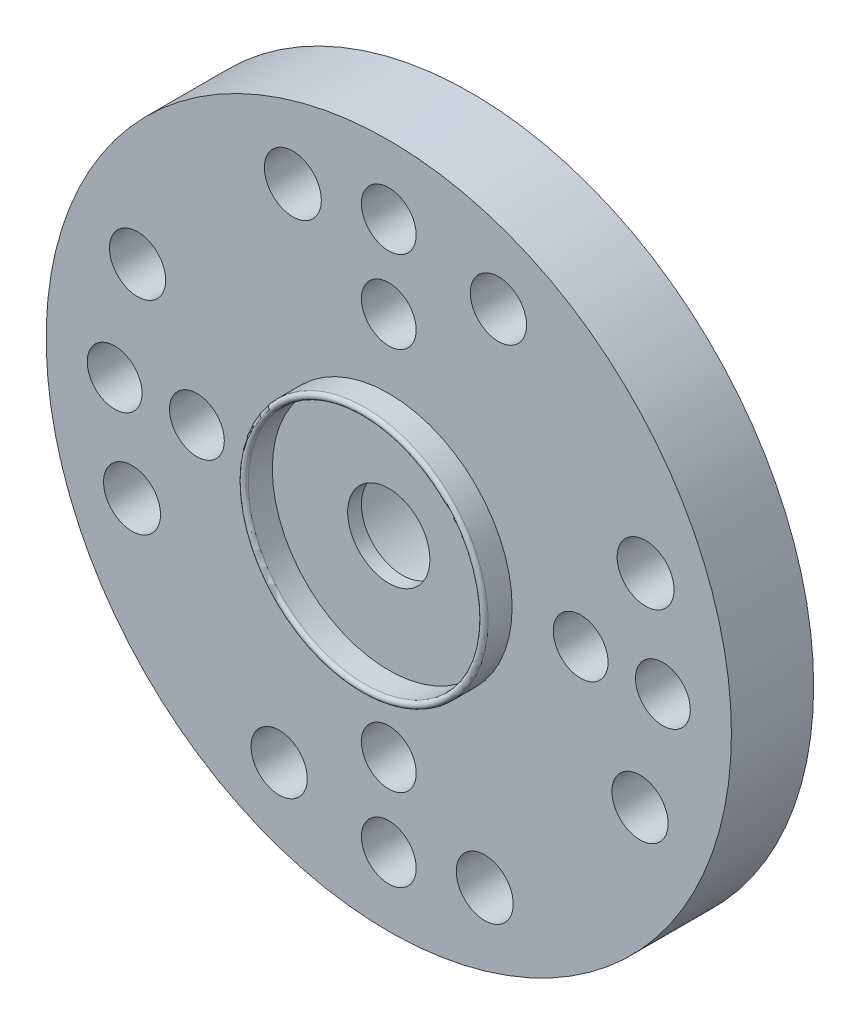
SolidWorks part; units mm, degrees
ref_plane "Plan de face" through (0, 0, 0) normal (0, 0, 1) x (1, 0, 0)
ref_plane "Plan de dessus" through (0, 0, 0) normal (0, 1, 0) x (1, 0, 0)
ref_plane "Plan de droite" through (0, 0, 0) normal (1, 0, 0) x (0, 0, -1)
sketch "Esquisse1" plane through (0, 0, 0) normal (0, 0, 1) x (1, 0, 0)
  circle A3 centre (0, 0) radius 12.5
  circle A4 centre (0, 0) radius 3
  circle A5 centre (0, 0) radius 2.75
  dimension "D1" = 25
  dimension "D2" = 6
  dimension "D3" = 5.5
extrude "Boss.-Extru.2" add sketch "Esquisse1" along normal blind 3 contours A3
sketch "Esquisse2" plane through (0, 0, 0) normal (0, 0, 1) x (1, 0, 0)
  circle A0 centre (0, 0) radius 4.5
  circle A1 centre (0, 0) radius 3
  dimension "D1" = 9
  dimension "D2" = 6
extrude "Enlèv. mat.-Extru.1" cut sketch "Esquisse2" along normal blind 2.5 contours A1
sketch "Esquisse3" plane through (0, 0, 0) normal (0, 0, -1) x (-1, 0, 0)
  circle A0 centre (0, 0) radius 1.5
  dimension "D1" = 3
extrude "Enlèv. mat.-Extru.2" cut sketch "Esquisse3" against normal blind 4.5
sketch "Esquisse5" plane through (0, 0, 0) normal (0, 0, -1) x (-1, 0, 0)
  circle A0 centre (0, 0) radius 4.5
  circle A1 centre (0, 0) radius 3
  dimension "D1" = 9
extrude "Boss.-Extru.3" add sketch "Esquisse5" along normal blind 4
sketch "Esquisse6" plane through (0, 0, 3) normal (0, 0, 1) x (1, 0, 0)
  circle A0 centre (0, 0) radius 4.5
  circle A1 centre (0, 0) radius 4.25
  dimension "D1" = 9
  dimension "D2" = 8.5
extrude "Boss.-Extru.4" add sketch "Esquisse6" along normal blind 1
fillet "Congé1" 2 edges at (4.5, 0, 4) (4.25, 0, 4) type full round first side face at (4.5, 0, 4) second side face at (4.25, 0, 4) middle face at (4.5, 0, 4)
sketch "Esquisse7" plane through (0, 0, 3) normal (0, 0, 1) x (1, 0, 0)
  line L0 (0, 12.735) -> (0, -13.511) construction
  line L1 (-13.04, 0) -> (13.4371, 0) construction
  circle A0 centre (0, 10) radius 1
  circle A1 centre (0, 7) radius 1
  circle A3 centre (4, 9.1652) radius 1.0258
  circle A4 centre (-3.5, 9.3675) radius 1.0392
  circle A5 centre (9.3675, 3.5) radius 1.0392
  circle A6 centre (10, 0) radius 1
  circle A7 centre (9.1652, -4) radius 1.0258
  circle A8 centre (7, 0) radius 1
  circle A9 centre (3.5, -9.3675) radius 1.0392
  circle A10 centre (0, -10) radius 1
  circle A11 centre (-4, -9.1652) radius 1.0258
  circle A12 centre (0, -7) radius 1
  circle A13 centre (-9.3675, -3.5) radius 1.0392
  circle A14 centre (-10, 0) radius 1
  circle A15 centre (-9.1652, 4) radius 1.0258
  circle A16 centre (-7, 0) radius 1
  point P43 (0, 0)
  dimension "D1" = 2
  dimension "D2" = 2
  dimension "D3" = 3.5
  dimension "D4" = 4
  dimension "D5" = 3
  dimension "D7" = 4
extrude "Enlèv. mat.-Extru.3" cut sketch "Esquisse7" against normal blind 8
equation "\"2.5.00mm\"=2"
